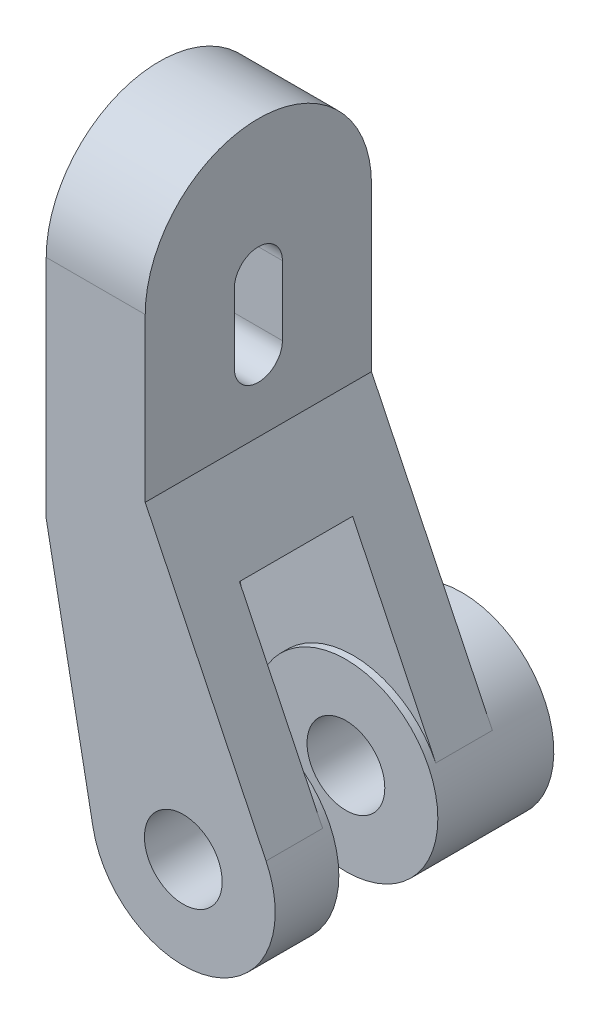
SolidWorks part; units mm, degrees
ref_plane "Plan de face" through (0, 0, 0) normal (0, 0, 1) x (1, 0, 0)
ref_plane "Plan de dessus" through (0, 0, 0) normal (0, 1, 0) x (1, 0, 0)
ref_plane "Plan de droite" through (0, 0, 0) normal (1, 0, 0) x (0, 0, -1)
sketch "Esquisse1" plane through (0, 0, 0) normal (1, 0, 0) x (0, 0, -1)
  line L0 (0, 4) -> (0, -4) construction
  line L1 (8, 4) -> (8, -4)
  line L2 (-8, 4) -> (-8, -4)
  arc A0 (8, 4) -> (-8, 4) centre (0, 4) ccw
  arc A1 (-8, -4) -> (8, -4) centre (0, -4) ccw
  point P8 (0, 0)
  dimension "D1" = 8
  dimension "D2" = 8
extrude "Boss.-Extru.1" add sketch "Esquisse1" along normal blind 7
hole_wizard "Dégagement M31" positions "Esquisse2" profile "Esquisse3" size "M3" standard "Ansi Metric" slot yes end condition through all
sketch "Esquisse2" plane through (7, 0, 0) normal (1, 0, 0) x (0, 0, -1)
  line L0 (0, -4.15) -> (0, 4.15) construction
  point P0 (0, 0)
  dimension "D1" = 8.3
sketch "Esquisse3" plane through (7, 0, 0) normal (0, 1, 0) x (0, 0, -1)
  line L0 (0, 0) -> (0, 7)
  line L1 (0, 7) -> (1.7, 7)
  line L2 (1.7, 7) -> (1.7, 0)
  line L5 (1.7, 0) -> (0, 0)
  line L11 (0, -6.35) -> (0, 107.95) construction
  dimension "Diamètre du perçage jusqu'au prochain" = 3.4
  dimension "Profondeur du perçage jusqu'au prochain" = 7
sketch "Esquisse6" plane through (7, 0, 0) normal (1, 0, 0) x (0, 0, -1)
  line L0 (-8, -4) -> (-8, -12)
  line L1 (-8, -12) -> (8, -12)
  line L2 (8, -4) -> (8, -12)
  arc A0 (-8, -4) -> (8, -4) centre (0, -4) ccw construction
  arc A1 (-8, -4) -> (8, -4) centre (0, -4) ccw
  arc M8 (-8, -4) -> (8, -4) centre (0, -4) ccw
extrude "Boss.-Extru.3" add sketch "Esquisse6" against normal through all contours L0 L1 M8 | L2 L1 M8 region at (7, -10.2131, 6.2131) region at (7, -10.2131, -6.2131)
sketch "Esquisse7" plane through (0, 0, 8) normal (0, 0, 1) x (1, 0, 0)
  line L0 (3.3079, -29.2442) -> (0, -12)
  line L1 (0, -12) -> (7, -12) construction
  line L2 (15.5447, -25.1929) -> (7, -7.5)
  line L3 (7, 4) -> (7, -12) construction
  line L4 (7, -12) -> (0, -12)
  line L7 (7, -12) -> (7, -7.5)
  arc A0 (3.3079, -29.2442) -> (15.5447, -25.1929) centre (9.6915, -28.0196) ccw
  dimension "D1" = 13
  dimension "D2" = 28.0196
  dimension "D3" = 9.6915
  dimension "D4" = 4.5
extrude "Boss.-Extru.4" add sketch "Esquisse7" against normal through all
sketch "Esquisse8" plane through (0, 0, 0) normal (0, 0, 1) x (1, 0, 0)
  circle A0 centre (9.6915, -28.0196) radius 15
  dimension "D1" = 30
extrude "Enlèv. mat.-Extru.1" cut sketch "Esquisse8" against normal mid plane 8
sketch "Esquisse9" plane through (0, 0, 4) normal (0, 0, -1) x (-1, 0, 0)
  circle A0 centre (-9.6915, -28.0196) radius 6.5
  arc A1 (-15.5447, -25.1929) -> (-3.3079, -29.2442) centre (-9.6915, -28.0196) ccw construction
extrude "Boss.-Extru.5" add sketch "Esquisse9" along normal blind 0.5
mirror "Symétrie1" about plane through (0, 0, 0) normal (0, 0, 1) of "Boss.-Extru.5"
hole_wizard "Dégagement M51" positions "Esquisse10" profile "Esquisse11" hole size "M5" standard "Ansi Metric" end condition through all
sketch "Esquisse10" plane through (0, 0, 8) normal (0, 0, 1) x (1, 0, 0)
  arc A0 (3.3079, -29.2442) -> (15.5447, -25.1929) centre (9.6915, -28.0196) ccw construction
  point P0 (9.6915, -28.0196)
sketch "Esquisse11" plane through (9.6915, -28.0196, 8) normal (1, 0, 0) x (0, -1, 0)
  line L0 (0, 0) -> (0, 16)
  line L1 (0, 16) -> (2.75, 16)
  line L2 (2.75, 16) -> (2.75, 0)
  line L5 (2.75, 0) -> (0, 0)
  line L11 (0, -6.35) -> (0, 107.95) construction
  dimension "Diamètre du perçage jusqu'au prochain" = 5.5
  dimension "Profondeur du perçage jusqu'au prochain" = 16
sketch "Esquisse12" plane through (0, 0, -8) normal (0, 0, -1) x (-1, 0, 0)
  line L1 (-4.6686, -28.0196) -> (-7.1801, -23.6696)
  line L2 (-7.1801, -23.6696) -> (-12.203, -23.6696)
  line L3 (-12.203, -23.6696) -> (-14.7145, -28.0196)
  line L4 (-14.7145, -28.0196) -> (-12.203, -32.3696)
  line L5 (-12.203, -32.3696) -> (-7.1801, -32.3696)
  line L6 (-7.1801, -32.3696) -> (-4.6686, -28.0196)
  circle A0 centre (-9.6915, -28.0196) radius 4.35 construction
  circle A1 centre (-9.6915, -28.0196) radius 6.5
  arc A2 (-15.5447, -25.1929) -> (-3.3079, -29.2442) centre (-9.6915, -28.0196) ccw construction
  dimension "D1" = 8.7
extrude "Boss.-Extru.6" add sketch "Esquisse12" along normal blind 3.7
mirror "Symétrie2" [suppressed] of bodies 110
delete or keep bodies "Corps-Supprimer/Garder 1" [suppressed] type delete bodies bodies 110
